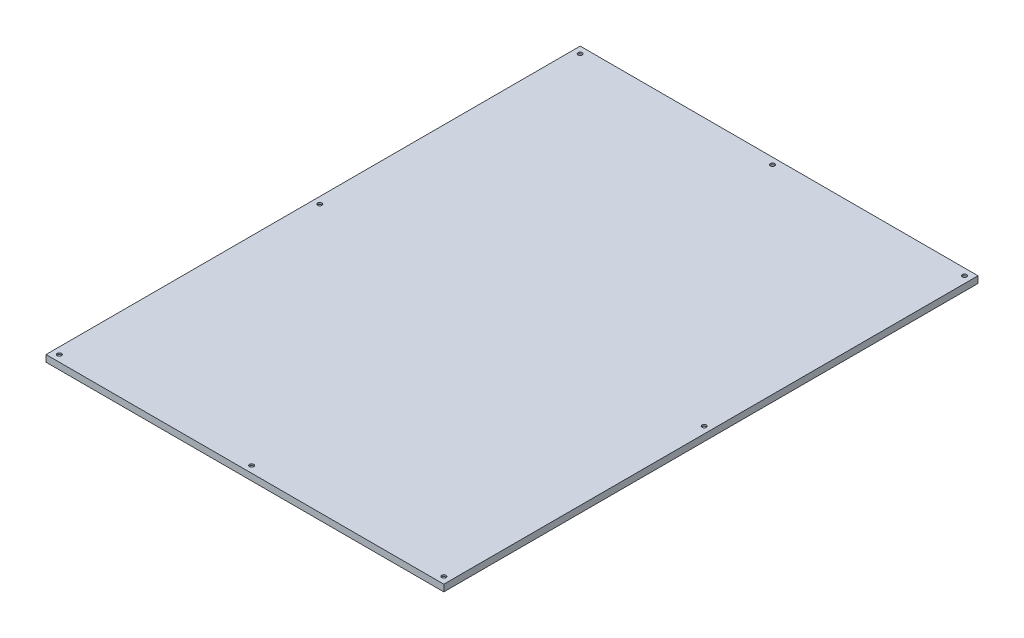
SolidWorks part; units mm, degrees
ref_plane "Front Plane" through (0, 0, 0) normal (0, 0, 1) x (1, 0, 0)
ref_plane "Top Plane" through (0, 0, 0) normal (0, 1, 0) x (1, 0, 0)
ref_plane "Right Plane" through (0, 0, 0) normal (1, 0, 0) x (0, 0, -1)
sketch "Sketch1" plane through (0, 0, 0) normal (0, 1, 0) x (1, 0, 0)
  line L1 (0, 0) -> (297.5, 0)
  line L2 (0, 0) -> (0, 399.5)
  line L3 (0, 399.5) -> (297.5, 399.5)
  line L4 (297.5, 0) -> (297.5, 399.5)
  dimension "D1" = 399.5
  dimension "D2" = 297.5
extrude "Boss-Extrude1" add sketch "Sketch1" along normal blind 5
sketch "Sketch2" plane through (0, 5, 0) normal (0, 1, 0) x (1, 0, 0)
  circle A0 centre (292.5, 199.75) radius 1.6 construction
  circle A1 centre (292.5, 5) radius 1.6 construction
  circle A2 centre (148.75, 5) radius 1.6 construction
  circle A3 centre (5, 5) radius 1.6 construction
  circle A4 centre (5, 199.75) radius 1.6 construction
  circle A5 centre (292.5, 394.5) radius 1.6 construction
  circle A6 centre (148.75, 394.5) radius 1.6 construction
  circle A7 centre (5, 394.5) radius 1.6 construction
  circle A8 centre (292.5, 199.75) radius 1.6
  circle A9 centre (292.5, 5) radius 1.6
  circle A10 centre (148.75, 5) radius 1.6
  circle A11 centre (5, 5) radius 1.6
  circle A12 centre (5, 199.75) radius 1.6
  circle A13 centre (292.5, 394.5) radius 1.6
  circle A14 centre (148.75, 394.5) radius 1.6
  circle A15 centre (5, 394.5) radius 1.6
extrude "Cut-Extrude1" cut sketch "Sketch2" against normal blind 1.2
